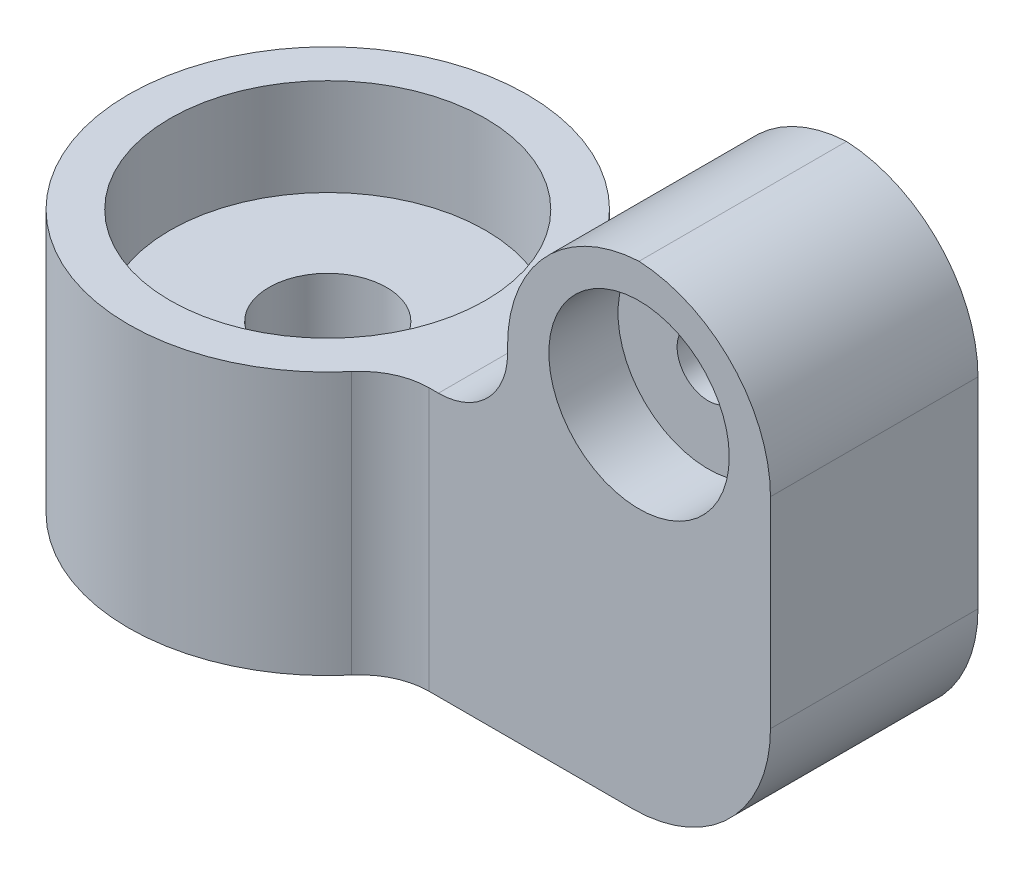
SolidWorks part; units mm, degrees
ref_plane "Front Plane" through (0, 0, 0) normal (0, 0, 1) x (1, 0, 0)
ref_plane "Top Plane" through (0, 0, 0) normal (0, 1, 0) x (1, 0, 0)
ref_plane "Right Plane" through (0, 0, 0) normal (1, 0, 0) x (0, 0, -1)
sketch "Sketch1" plane through (0, 0, 0) normal (0, 0, 1) x (1, 0, 0)
  line L0 (-9.5, 9) -> (9.5, 9)
  line L1 (9.5, 9) -> (9.5, -25.52)
  line L2 (9.5, -25.52) -> (-30, -25.52)
  line L3 (-30, -25.52) -> (-30, -6.52)
  line L4 (-30, -6.52) -> (-9.5, -6.52)
  line L5 (-9.5, -6.52) -> (-9.5, 9)
  line L6 (-16.2026, -6.52) -> (19.4501, -6.52) construction
  circle A0 centre (0, 0) radius 2.25
  circle A1 centre (0, 0) radius 6.52
  point P10 (0, 9)
  dimension "D1" = 4.5
  dimension "D4" = 13.04
  dimension "D2" = 19
  dimension "D3" = 9
  dimension "D5" = 30
  dimension "D7" = 19
extrude "Boss-Extrude1" add sketch "Sketch1" along normal mid plane 15 contours L6 L4 L3 L2 L1 | L5 L6 A1 L1 L0 | A1 A0 region at (-4.4799, 4.4799, 0) region at (0, 8.7547, 0) region at (-10.25, -16.02, 0)
extrude "Cut-Extrude1" cut sketch "Sketch1<3>" against normal blind 5 from surface contours A1 starting at face at (-10, -7.68, 7.5)
sketch "Sketch1<3>" plane through (0, 0, 0) normal (0, 0, 1) x (1, 0, 0) same geometry as "Sketch1"
extrude "Cut-Extrude2" cut sketch "Sketch1<4>" along normal blind 5 from surface contours A1 starting at face at (-10, -7.68, -7.5)
sketch "Sketch1<4>" plane through (0, 0, 0) normal (0, 0, 1) x (1, 0, 0) same geometry as "Sketch1"
sketch "Sketch2" plane through (0, -6.52, 0) normal (0, 1, 0) x (1, 0, 0)
  line L0 (-30, -7.5) -> (-30, 7.5) construction
  circle A0 centre (-30, 0) radius 11.4
  circle A1 centre (-30, 0) radius 4.25
  circle A2 centre (-30, 0) radius 14.4
  line M1 (-9.5, 7.5) -> (-30, 7.5)
  line M2 (-30, 7.5) -> (-30, -7.5)
  line M3 (-30, -7.5) -> (-9.5, -7.5)
  dimension "D1" = 22.8
  dimension "D2" = 8.5
  dimension "D3" = 3
extrude "Boss-Extrude2" add sketch "Sketch2" against normal through all contours A2
extrude "Cut-Extrude3" cut sketch "Sketch2<3>" against normal through all both and the other way through all contours A1 M2 | A1 M2 region at (-28.1962, -6.52, 0) region at (-31.8038, -6.52, 0)
sketch "Sketch2<3>" plane through (0, -6.52, 0) normal (0, 1, 0) x (1, 0, 0) same geometry as "Sketch2"
extrude "Cut-Extrude4" cut sketch "Sketch2<4>" against normal blind 7 from surface contours A1 A0 M2 M1 M3 | A1 A0 M2 M3 M1 region at (-23.9466, -6.52, 0) region at (-25.7073, -6.52, -7.8032) starting at face at (-30, -6.52, 4.25)
sketch "Sketch2<4>" plane through (0, -6.52, 0) normal (0, 1, 0) x (1, 0, 0) same geometry as "Sketch2"
extrude "Cut-Extrude5" cut sketch "Sketch2<5>" along normal blind 7 from surface contours A0 starting at face at (-30, -25.52, 4.25)
sketch "Sketch2<5>" plane through (0, -6.52, 0) normal (0, 1, 0) x (1, 0, 0) same geometry as "Sketch2"
fillet "Fillet1" radius 5 3 edges at (-17.7073, -16.02, -7.5) (-9.5, -6.52, 0) (-17.7073, -16.02, 7.5)
fillet "Fillet2" radius 10 3 edges at (-9.5, 9, 0) (9.5, 9, 0) (9.5, -25.52, 0)
